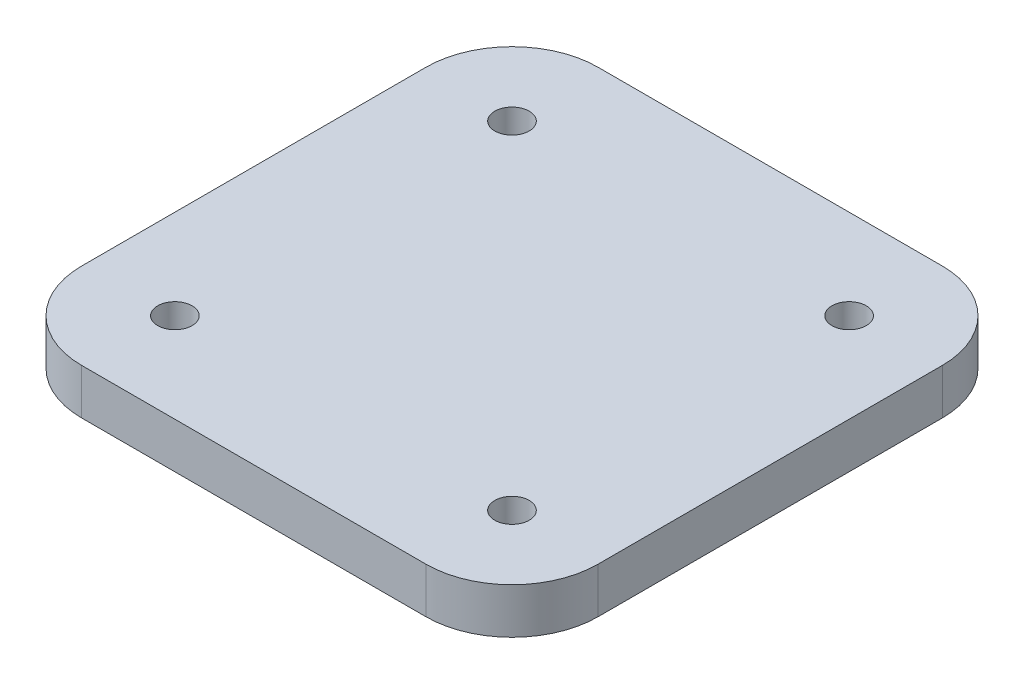
SolidWorks part; units mm, degrees
ref_plane "Front Plane" through (0, 0, 0) normal (0, 0, 1) x (1, 0, 0)
ref_plane "Top Plane" through (0, 0, 0) normal (0, 1, 0) x (1, 0, 0)
ref_plane "Right Plane" through (0, 0, 0) normal (1, 0, 0) x (0, 0, -1)
sketch "Sketch1" plane through (0, 0, 0) normal (0, 1, 0) x (1, 0, 0)
  line L1 (-24, -36) -> (24, -36)
  line L2 (-36, -24) -> (-36, 24)
  line L3 (-24, 36) -> (24, 36)
  line L4 (36, -24) -> (36, 24)
  line L5 (-36, -36) -> (36, 36) construction
  line L6 (-36, 36) -> (36, -36) construction
  arc A0 (24, 36) -> (36, 24) centre (24, 24) cw
  arc A1 (24, -36) -> (36, -24) centre (24, -24) ccw
  arc A2 (-24, -36) -> (-36, -24) centre (-24, -24) cw
  arc A3 (-36, 24) -> (-24, 36) centre (-24, 24) cw
  point P0 (0, 0)
  dimension "D1" = 12
  dimension "D2" = 72
  dimension "D3" = 72
extrude "Boss-Extrude1" add sketch "Sketch1" along normal blind 6.35
sketch "Sketch2" plane through (0, 6.35, 0) normal (0, 1, 0) x (1, 0, 0)
  line L0 (-36, 0) -> (36, 0) construction
  line L1 (-36, 24) -> (-36, -24) construction
  line L2 (36, -24) -> (36, 24) construction
  line L3 (-36, 12) -> (36, 12) construction
  line L5 (23.5, -23.5) -> (-23.5, -23.5) construction
  line L6 (23.5, -23.5) -> (23.5, 23.5) construction
  line L7 (23.5, 23.5) -> (-23.5, 23.5) construction
  line L8 (-23.5, -23.5) -> (-23.5, 23.5) construction
  line L9 (23.5, -23.5) -> (-23.5, 23.5) construction
  line L10 (23.5, 23.5) -> (-23.5, -23.5) construction
  circle A1 centre (-23.5, 23.5) radius 2.4
  circle A3 centre (23.5, 23.5) radius 2.4
  circle A4 centre (23.5, -23.5) radius 2.4
  circle A5 centre (-23.5, -23.5) radius 2.4
  point P16 (0, 0)
  dimension "D3" = 4.8
  dimension "D1" = 47
  dimension "D2" = 2
  dimension "D4" = 2
extrude "Cut-Extrude1" cut sketch "Sketch2" against normal through all
sketch "Sketch3" [suppressed] plane through (0, 6.35, 0) normal (0, 1, 0) x (1, 0, 0)
  line L0 (0, 0) -> (-36, 0) construction
  line L1 (-36, 24) -> (-36, -24) construction
  line L3 (-33.5, -8) -> (-18.5, -8) construction
  line L4 (-33.5, -8) -> (-33.5, 8) construction
  line L5 (-33.5, 8) -> (-18.5, 8) construction
  line L6 (-18.5, -8) -> (-18.5, 8) construction
  line L7 (-33.5, -8) -> (-18.5, 8) construction
  line L8 (-33.5, 8) -> (-18.5, -8) construction
  circle A0 centre (-33.5, 8) radius 1.5
  circle A1 centre (-18.5, 8) radius 1.5
  circle A2 centre (-18.5, -8) radius 1.5
  circle A3 centre (-33.5, -8) radius 1.5
  point P5 (-26, 0)
  dimension "D4" = 3
  dimension "D1" = 15
  dimension "D2" = 16
  dimension "D3" = 2.5
extrude "Cut-Extrude2" [suppressed] cut sketch "Sketch3" against normal through all
